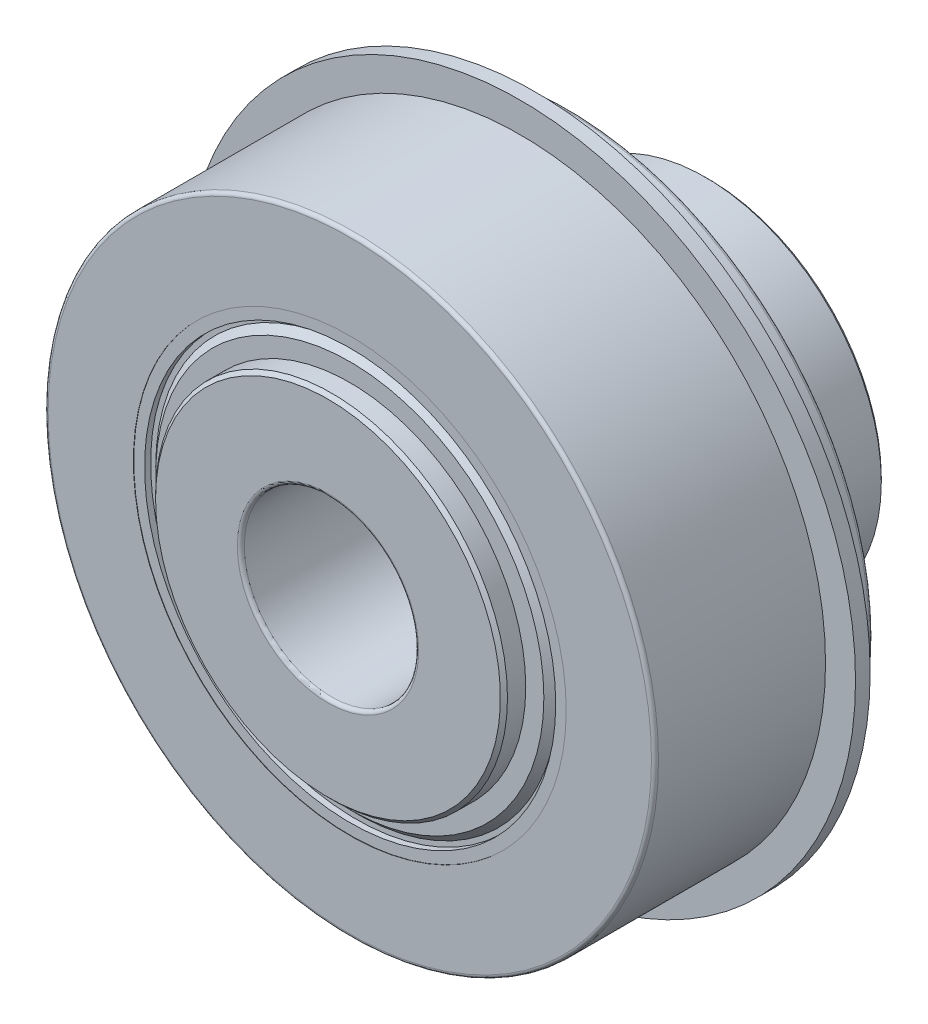
SolidWorks part; units mm, degrees
note: '?' marks a value the reader was unsure of.
ref_plane "Front Plane" through (0, 0, 0) normal (0, 0, 1) x (1, 0, 0)
ref_plane "Top Plane" through (0, 0, 0) normal (0, 1, 0) x (1, 0, 0)
ref_plane "Right Plane" through (0, 0, 0) normal (1, 0, 0) x (0, 0, -1)
sketch "Sketch1" plane through (0, 0, 0) normal (1, 0, 0) x (0, 0, -1)
  line L0 (-9.525, 0) -> (9.525, 0) construction
  line L1 (0, 0) -> (0, 22.225) construction
  line L2 (-3.6852, 15.7607) -> (3.6852, 15.7607) construction
  line L3 (-9.525, 12.8143) -> (18.2118, 12.8143) construction
  line L4 (-9.525, 12.8143) -> (-9.525, 6.35)
  line L5 (-9.525, 6.35) -> (18.2118, 6.35)
  line L7 (-7.9375, 15.7607) -> (7.9375, 15.7607) construction
  line L8 (-7.9375, 15.7607) -> (-7.9375, 22.225) construction
  line L9 (-7.9375, 22.225) -> (7.9375, 22.225) construction
  line L10 (7.9375, 15.7607) -> (7.9375, 22.225) construction
  line L11 (-3.6852, 12.8143) -> (3.6852, 12.8143) construction
  line L12 (0, 18.2562) -> (0, 22.225) construction
  line L13 (4.4831, 21.5786) -> (5.5499, 21.5786) construction
  line L14 (4.4831, 21.5786) -> (4.4831, 24.4094) construction
  line L15 (4.4831, 24.4094) -> (5.5499, 24.4094) construction
  line L16 (5.5499, 21.5786) -> (5.5499, 24.4094) construction
  line L17 (0, 18.2562) -> (0, 14.2875) construction
  line L18 (3.6852, 12.8143) -> (18.2118, 12.8143)
  line L19 (-9.525, 12.8143) -> (-3.6852, 12.8143)
  line L20 (18.2118, 6.35) -> (18.2118, 12.8143)
  circle A0 centre (0, 14.2875) radius 3.9688 construction
  arc A1 (-3.6852, 12.8143) -> (3.6852, 12.8143) centre (0, 14.2875) ccw
  point P5 (0, 6.35)
  dimension "D1" = 9.525
  dimension "OD" = 44.45
  dimension "Shaft Dia" = 12.7
  dimension "F" = 25.6286
  dimension "A" = 1.5875
  dimension "D2" = 0.6464
  dimension "H" = 1.0668
  dimension "D3" = 6.4643
  dimension "P" = 48.8188
  dimension "B" = 15.875
  dimension "overall" = 27.7368
  dimension "G" = 3.4544
revolve "Revolve1" add sketch "Sketch1" angle 360 about L0
sketch "Sketch3" plane through (0, 0, 0) normal (1, 0, 0) x (0, 0, -1)
  line L0 (-3.6852, 15.7607) -> (-7.9375, 15.7607)
  line L1 (-7.9375, 15.7607) -> (-7.9375, 22.225)
  line L2 (-7.9375, 22.225) -> (4.4831, 22.225)
  line L3 (-7.9375, 22.225) -> (7.9375, 22.225) construction
  line L4 (4.4831, 22.225) -> (4.4831, 21.5786)
  line L5 (4.4831, 21.5786) -> (5.5499, 21.5786)
  line L6 (5.5499, 21.5786) -> (5.5499, 22.225)
  line L7 (7.9375, 22.225) -> (7.9375, 15.7607)
  line L8 (7.9375, 15.7607) -> (3.6852, 15.7607)
  line L9 (5.5499, 22.225) -> (7.9375, 22.225)
  arc A0 (-3.6852, 15.7607) -> (3.6852, 15.7607) centre (0, 14.2875) cw
revolve "Revolve2" add sketch "Sketch3" angle 360 about L0
sketch "Sketch4" plane through (0, 0, 0) normal (1, 0, 0) x (0, 0, -1)
  line L1 (4.4831, 24.4094) -> (5.5499, 24.4094)
  line L2 (4.4831, 24.4094) -> (4.4831, 21.5786)
  line L3 (4.4831, 21.5786) -> (5.5499, 21.5786)
  line L4 (5.5499, 24.4094) -> (5.5499, 21.5786)
revolve "Revolve3" add sketch "Sketch4" angle 360 about L0
sketch "Sketch5" plane through (0, 0, 0) normal (1, 0, 0) x (0, 0, -1)
  line L0 (-7.9375, 14.133) -> (-7.9375, 12.8143)
  line L1 (-9.525, 12.8143) -> (-3.6852, 12.8143) construction
  line L2 (-7.9375, 22.225) -> (-7.9375, -22.225) construction
  line L3 (-7.9375, 14.133) -> (-7.4459, 14.6246)
  line L4 (-7.4459, 14.6246) -> (-7.4459, 15.3199)
  line L5 (-7.4459, 15.3199) -> (-7.4713, 15.3199)
  line L6 (-7.4713, 15.3199) -> (-7.4713, 14.9722)
  line L7 (-7.4713, 14.9722) -> (-7.9121, 14.9722)
  line L8 (-7.9121, 14.9722) -> (-7.9121, 15.7607)
  line L9 (-7.9375, 15.7607) -> (7.9375, 15.7607) construction
  line L10 (-7.9121, 15.7607) -> (-7.005, 15.7607)
  line L11 (-7.005, 15.7607) -> (-7.005, 14.442)
  line L12 (-7.005, 14.442) -> (-7.4967, 13.9504)
  line L13 (-7.4967, 13.9504) -> (-7.4967, 12.8143)
  line L14 (-7.9375, 12.8143) -> (-7.4967, 12.8143)
  line L15 (0, 22.225) -> (0, 25.0558) construction
  line L16 (-7.9375, 22.225) -> (7.9375, 22.225) construction
  line L17 (-7.4586, 15.3199) -> (-7.4586, 15.7607) construction
  line L18 (-7.6917, 14.3788) -> (-7.38, 14.0671) construction
  line L19 (-7.4459, 14.9722) -> (-7.005, 14.9722) construction
  line L20 (-7.9121, 15.7607) -> (-7.9375, 15.7607) construction
  line L21 (7.9121, 15.7607) -> (7.9375, 15.7607) construction
  line L22 (7.4459, 14.9722) -> (7.005, 14.9722) construction
  line L23 (7.6917, 14.3788) -> (7.38, 14.0671) construction
  line L24 (7.4586, 15.3199) -> (7.4586, 15.7607) construction
  line L25 (7.9375, 12.8143) -> (7.4967, 12.8143)
  line L26 (7.4967, 13.9504) -> (7.4967, 12.8143)
  line L27 (7.005, 14.442) -> (7.4967, 13.9504)
  line L28 (7.005, 15.7607) -> (7.005, 14.442)
  line L29 (7.9121, 15.7607) -> (7.005, 15.7607)
  line L30 (7.9121, 14.9722) -> (7.9121, 15.7607)
  line L31 (7.4713, 14.9722) -> (7.9121, 14.9722)
  line L32 (7.4713, 15.3199) -> (7.4713, 14.9722)
  line L33 (7.4459, 15.3199) -> (7.4713, 15.3199)
  line L34 (7.4459, 14.6246) -> (7.4459, 15.3199)
  line L35 (7.9375, 14.133) -> (7.4459, 14.6246)
  line L36 (7.9375, 14.133) -> (7.9375, 12.8143)
  line L37 (4.4831, 21.5786) -> (4.4831, 24.4094) construction
  point P0 (-7.4459, 14.9722)
  dimension "D1" = 45
  dimension "D2" = 0.0254
revolve "Revolve4" add sketch "Sketch5" angle 360 about L0
sketch "Sketch7" plane through (0, 0, 0) normal (1, 0, 0) x (0, 0, -1)
  line L0 (3.6852, 12.8143) -> (18.2118, 12.8143) construction
  line L1 (12.2936, 12.8143) -> (14.7066, 12.8143)
  line L2 (12.2936, 12.8143) -> (12.2936, 0)
  line L3 (12.2936, 0) -> (14.7066, 0)
  line L4 (14.7066, 12.8143) -> (14.7066, 0)
  line L5 (-9.525, 0) -> (9.525, 0) construction
  line L6 (12.2936, 12.8143) -> (12.2936, 15.7607) construction
  line L7 (-7.9375, 15.7607) -> (7.9375, 15.7607) construction
  dimension "Screw Dia" = 4.826
  dimension "M" = 5.9182
revolve "Cut-Revolve2" cut sketch "Sketch7" angle 360 about L2
sketch "Sketch8" plane through (0, 0, 0) normal (1, 0, 0) x (0, 0, -1)
  line L0 (12.2936, 12.8143) -> (12.2936, 0) construction
  line L1 (12.2936, 6.984) -> (14.7066, 6.984)
  line L2 (12.2936, 6.984) -> (12.2936, 13.3223)
  line L3 (12.2936, 13.3223) -> (14.7066, 13.3223)
  line L4 (14.7066, 6.984) -> (14.7066, 13.3223)
  line L5 (14.7066, 12.8143) -> (14.7066, 0) construction
  line L7 (-9.525, 6.35) -> (18.2118, 6.35) construction
  dimension "D1" = 6.3383
  dimension "D2" = 0.634
  dimension "D3" = 0.508
revolve "Revolve5" add sketch "Sketch8" angle 360 about L2
sketch "Sketch9" plane through (0, 13.3223, 0) normal (0, 1, 0) x (-1, 0, 0)
  line L0 (0, 9.525) -> (0, -18.2118) construction
  line L1 (0, -13.6867) -> (1.2065, -12.9902)
  line L2 (1.2065, -12.9902) -> (1.2065, -11.597)
  line L3 (1.2065, -11.597) -> (0, -10.9005)
  line L4 (0, -10.9005) -> (-1.2065, -11.597)
  line L5 (-1.2065, -11.597) -> (-1.2065, -12.9902)
  line L6 (-1.2065, -12.9902) -> (0, -13.6867)
  circle A0 centre (0, -12.2936) radius 1.2065 construction
  dimension "D1" = 2.413
extrude "Cut-Extrude1" cut sketch "Sketch9" against normal blind 1.5846
chamfer "Chamfer1" distance 0.2413 angle 45 1 edges at (0, 13.3223, -9.8806)
ref_axis "Axis1" through (0, 0, -9.525) along (0, 0, 1)?
pattern_circular "CirPattern1" count 2 every 120 about axis through (0, 0, -9.525) along (0, 0, 1) of "Cut-Revolve2"
pattern_circular "CirPattern2" count 2 every 120 about axis through (0, 0, 0) along (0, 0, 1) of bodies 355
chamfer "Chamfer2" distance 0.2563 angle 45 2 edges at (12.8143, 0, -18.2118) (12.8143, 0, 9.525)
fillet "Fillet1" radius 0.2563 2 edges at (6.35, 0, -18.2118) (6.35, 0, 9.525)
fillet "Fillet2" radius 0.2563 2 edges at (22.225, 0, -7.9375) (22.225, 0, 7.9375)
delete or keep bodies "Body-Delete1" [suppressed] type delete bodies bodies 349
equation "\"D2@Sketch1\" = \"D3@Sketch1\"*.1"
equation "\"D2@Sketch8\" = \"D1@Sketch8\"*.1"
equation "\"D1@Sketch9\" = \"Screw Dia@Sketch7\"/2"
equation "\"D1@Cut-Extrude1\" = \"D1@Sketch8\"/4"
equation "\"D1@Chamfer1\" = \"Screw Dia@Sketch7\"*.05"
equation "\"D1@Chamfer2\" = \"F@Sketch1\"*.01"
equation "\"D1@Fillet1\" = \"D1@Chamfer2\""
equation "\"D1@Fillet2\" = \"D1@Fillet1\""
equation "\"D1@Sketch1\" = \"B@Sketch1\"/2+\"A@Sketch1\""
